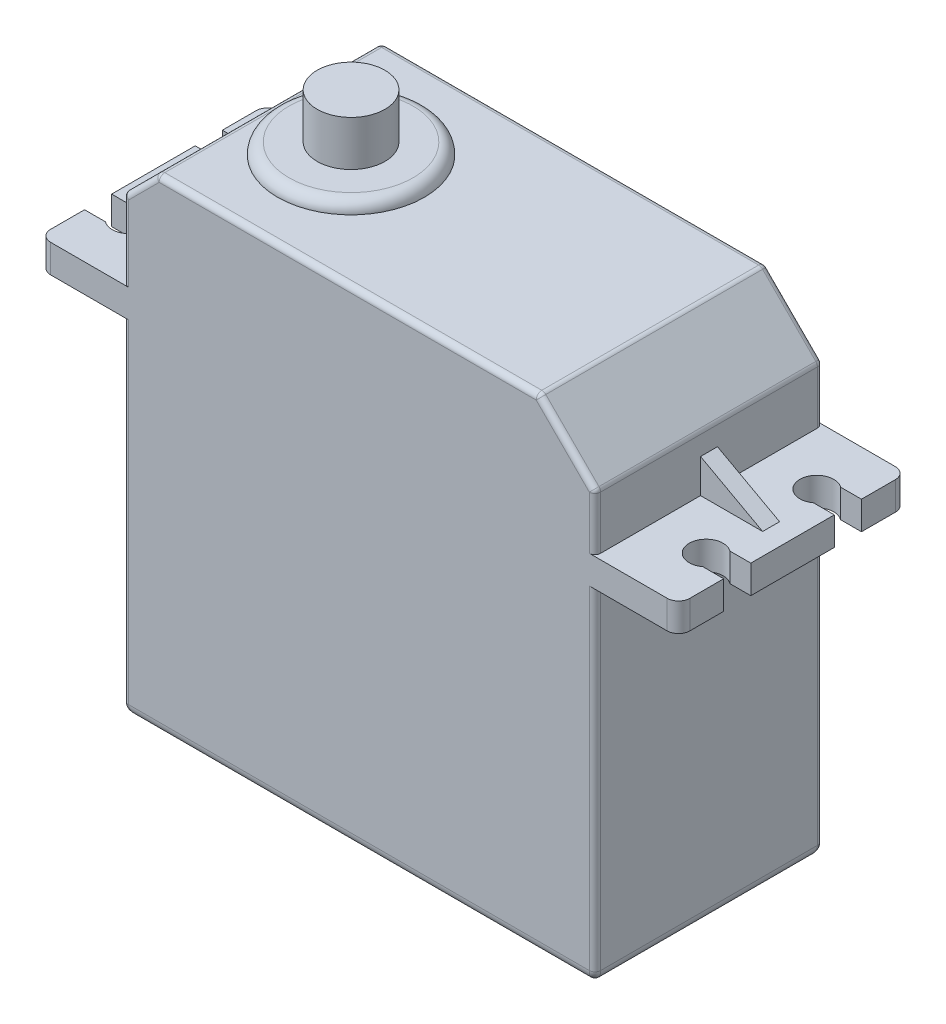
SolidWorks part; units mm, degrees
material "SavoxSW-0231MG"
ref_plane "Front Plane" through (0, 0, 0) normal (0, 0, 1) x (1, 0, 0)
ref_plane "Top Plane" through (0, 0, 0) normal (0, 1, 0) x (1, 0, 0)
ref_plane "Right Plane" through (0, 0, 0) normal (1, 0, 0) x (0, 0, -1)
sketch "Sketch1" plane through (0, 0, 0) normal (0, 0, 1) x (1, 0, 0)
  line L0 (0, 0) -> (41.8, 0)
  line L1 (0, 0) -> (0, 30.5)
  line L2 (0, 30.5) -> (-7.4, 30.5)
  line L3 (-7.4, 30.5) -> (-7.4, 33)
  line L4 (-7.4, 33) -> (0, 33)
  line L5 (0, 33) -> (0, 39.9)
  line L6 (3, 42.9) -> (36.8, 42.9)
  line L7 (41.8, 37.9) -> (41.8, 33)
  line L8 (41.8, 33) -> (49.2, 33)
  line L9 (49.2, 33) -> (49.2, 30.5)
  line L10 (49.2, 30.5) -> (41.8, 30.5)
  line L11 (41.8, 30.5) -> (41.8, 0)
  line L12 (0, 39.9) -> (3, 42.9)
  line L13 (36.8, 42.9) -> (41.8, 37.9)
  point P7 (0, 42.9)
  point P8 (41.8, 42.9)
  dimension "D1" = 41.8
  dimension "D2" = 30.5
  dimension "D3" = 2.5
  dimension "D4" = 42.9
  dimension "D5" = 7.4
extrude "Boss-Extrude1" add sketch "Sketch1" along normal blind 20.2
fillet "Fillet1" radius 1 4 edges at (49.2, 31.75, 20.2) (49.2, 31.75, 0) (-7.4, 31.75, 0) (-7.4, 31.75, 20.2)
sketch "Sketch2" plane through (0, 33, 0) normal (0, 1, 0) x (1, 0, 0)
  line L0 (-7.4, -19.2) -> (-7.4, -1) construction
  line L1 (49.2, -19.2) -> (49.2, -1) construction
  line L2 (-7.4, -4) -> (-5.55, -4)
  line L3 (-7.4, -6.4) -> (-5.55, -6.4)
  line L4 (-7.4, -4) -> (-7.4, -6.4)
  line L5 (-5.55, -13.8) -> (-7.4, -13.8)
  line L6 (-5.55, -16.2) -> (-7.4, -16.2)
  line L7 (-7.4, -13.8) -> (-7.4, -16.2)
  line L8 (47.35, -4) -> (49.2, -4)
  line L9 (47.35, -6.4) -> (49.2, -6.4)
  line L10 (49.2, -4) -> (49.2, -6.4)
  line L11 (47.35, -13.8) -> (49.2, -13.8)
  line L12 (47.35, -16.2) -> (49.2, -16.2)
  line L13 (49.2, -13.8) -> (49.2, -16.2)
  arc A0 (-5.55, -16.2) -> (-5.55, -13.8) centre (-4.65, -15) ccw
  arc A1 (-5.55, -6.4) -> (-5.55, -4) centre (-4.65, -5.2) ccw
  arc A2 (47.35, -4) -> (47.35, -6.4) centre (46.45, -5.2) ccw
  arc A3 (47.35, -13.8) -> (47.35, -16.2) centre (46.45, -15) ccw
  dimension "D1" = 3
  dimension "D2" = 9.8
  dimension "D3" = 5.2
  dimension "D4" = 2.75
  dimension "D6" = 1.2
  dimension "D7" = 1.2
  dimension "D8" = 1.2
  dimension "D9" = 1.2
  dimension "D10" = 1.2
  dimension "D11" = 1.2
  dimension "D12" = 1.2
  dimension "D13" = 1.2
extrude "Cut-Extrude1" cut sketch "Sketch2" against normal through all
sketch "Sketch3" plane through (0, 42.9, 0) normal (0, 1, 0) x (1, 0, 0)
  circle A0 centre (10.1, -10.1) radius 6.5
  dimension "D1" = 13
  dimension "D2" = 10.1
  dimension "D3" = 10.1
extrude "Boss-Extrude2" add sketch "Sketch3" along normal blind 1
fillet "Fillet2" radius 1 4 edges at (20.9, 0, 20.2) (41.8, 0, 10.1) (20.9, 0, 0) (0, 0, 10.1)
ref_plane "Plane1" through (0, 0, 10.1) normal (0, 0, 1) x (1, 0, 0)
sketch "Sketch4" plane through (0, 0, 10.1) normal (0, 0, 1) x (1, 0, 0)
  line L0 (-5.5, 33) -> (0, 36)
  line L1 (0, 33) -> (-6.4, 33) construction
  line L2 (0, 39.9) -> (0, 33) construction
  line L3 (0, 36) -> (0, 33)
  line L4 (0, 33) -> (-5.5, 33)
  line L5 (41.8, 33) -> (47.3, 33)
  line L7 (47.3, 33) -> (41.8, 36)
  line L9 (41.8, 36) -> (41.8, 33)
  line L10 (48.2, 33) -> (41.8, 33) construction
  dimension "D1" = 5.5
  dimension "D2" = 3
extrude "Boss-Extrude3" add sketch "Sketch4" along normal mid plane 1.5
fillet "Fillet3" radius 0.5 22 edges at (0.2929, 0.2929, 19.9071) (0.2929, 0.2929, 0.2929) (41.5071, 0.2929, 19.9071) (41.5071, 0.2929, 0.2929) (0, 39.9, 10.1) (3, 42.9, 10.1) (36.8, 42.9, 10.1) (41.8, 37.9, 10.1) (41.8, 35.45, 20.2) (39.3, 40.4, 20.2) (19.9, 42.9, 20.2) (1.5, 41.4, 20.2) (0, 36.45, 20.2) (0, 15.75, 20.2) (0, 15.75, 0) (0, 36.45, 0) (1.5, 41.4, 0) (39.3, 40.4, 0) (19.9, 42.9, 0) (41.8, 35.45, 0) (41.8, 15.75, 20.2) (41.8, 15.75, 0)
fillet "Fillet4" radius 1 1 edges at (10.1, 43.9, 16.6)
sketch "Sketch5" plane through (0, 43.9, 0) normal (0, 1, 0) x (1, 0, 0)
  circle A0 centre (10.1, -10.1) radius 3
  dimension "D1" = 6
extrude "Boss-Extrude4" add sketch "Sketch5" along normal blind 4
sketch "Sketch6" plane through (0, 0, 0) normal (-1, 0, 0) x (0, 0, 1)
  circle A0 centre (10.1, 6) radius 3.5
  dimension "D1" = 7
  dimension "D2" = 10.1
  dimension "D3" = 6
extrude "Boss-Extrude5" add sketch "Sketch6" along normal blind 0.01
